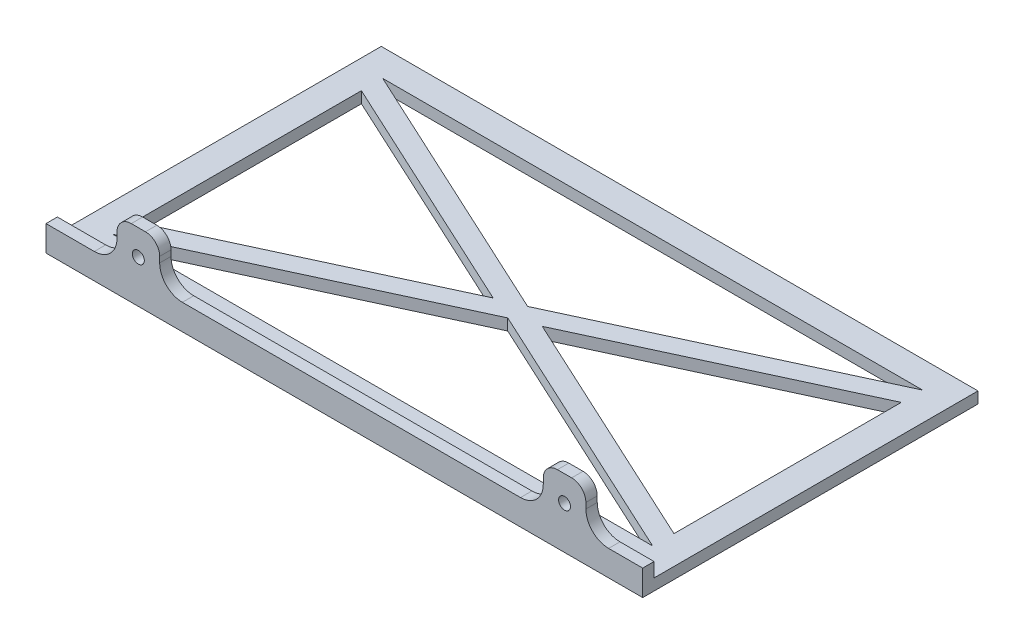
SolidWorks part; units mm, degrees
ref_plane "Спереди" through (0, 0, 0) normal (0, 0, 1) x (1, 0, 0)
ref_plane "Сверху" through (0, 0, 0) normal (0, 1, 0) x (1, 0, 0)
ref_plane "Справа" through (0, 0, 0) normal (1, 0, 0) x (0, 0, -1)
sketch "Эскиз1" plane through (0, 0, 0) normal (0, 1, 0) x (1, 0, 0)
  line L1 (-149.2777, 83.4643) -> (60.7223, 83.4643)
  line L2 (-149.2777, 83.4643) -> (-149.2777, -30.5357)
  line L3 (-149.2777, -30.5357) -> (60.7223, -30.5357)
  line L4 (60.7223, 83.4643) -> (60.7223, -30.5357)
  line L5 (-149.2777, 83.4643) -> (60.7223, -30.5357) construction
  line L6 (-149.2777, -30.5357) -> (60.7223, 83.4643) construction
  point P0 (-44.2777, 26.4643)
  dimension "D1" = 114
  dimension "D2" = 210
extrude "Бобышка-Вытянуть1" add sketch "Эскиз1" along normal blind 4
sketch "Эскиз2" plane through (0, 4, 0) normal (0, 1, 0) x (1, 0, 0)
  line L0 (-139.2777, 73.9643) -> (50.7223, 73.9643)
  line L1 (50.7223, 73.9643) -> (-44.2777, 29.9643)
  line L2 (-44.2777, 29.9643) -> (-139.2777, 73.9643)
  line L3 (-139.2777, -21.0357) -> (50.7223, -21.0357)
  line L4 (50.7223, -21.0357) -> (-44.2777, 22.9643)
  line L5 (-44.2777, 22.9643) -> (-139.2777, -21.0357)
  line L6 (-139.2777, 66.4643) -> (-52.914, 26.4643)
  line L7 (-52.914, 26.4643) -> (-139.2777, -13.5357)
  line L8 (-139.2777, -13.5357) -> (-139.2777, 66.4643)
  line L9 (-35.6413, 26.4643) -> (50.7223, 66.4643)
  line L10 (50.7223, 66.4643) -> (50.7223, -13.5357)
  line L11 (50.7223, -13.5357) -> (-35.6413, 26.4643)
  line L12 (60.7223, 83.4643) -> (-149.2777, 83.4643) construction
  line L13 (-149.2777, -30.5357) -> (60.7223, -30.5357) construction
  line L14 (60.7223, -30.5357) -> (60.7223, 83.4643) construction
  point P11 (-44.2777, 73.9643)
  point P15 (-44.2777, 83.4643)
  point P16 (0, 0)
  point P17 (-44.2777, -21.0357)
  point P20 (-44.2777, -30.5357)
  point P21 (-139.2777, 26.4643)
  point P22 (50.7223, 26.4643)
  point P25 (60.7223, 26.4643)
  point P26 (0, 0)
  dimension "D1" = 190
  dimension "D2" = 80
  dimension "D3" = 44
  dimension "D4" = 44
  dimension "D5" = 7
  dimension "D6" = 9.5
  dimension "D7" = 9.5
extrude "Вырез-Вытянуть1" cut sketch "Эскиз2" against normal through all
sketch "Эскиз5" plane through (0, 0, 30.5357) normal (0, 0, 1) x (1, 0, 0)
  line L0 (-149.2777, 0) -> (60.7223, 0)
  line L1 (60.7223, 0) -> (60.7223, 9)
  line L2 (60.7223, 9) -> (-149.2777, 9)
  line L3 (-149.2777, 9) -> (-149.2777, 0)
  dimension "D1" = 210
  dimension "D2" = 9
extrude "Бобышка-Вытянуть3" add sketch "Эскиз5" along normal blind 4
sketch "Эскиз6" plane through (0, 0, 34.5357) normal (0, 0, 1) x (1, 0, 0)
  line L0 (-124.2777, 9) -> (-124.2777, 24)
  line L1 (60.7223, 9) -> (-149.2777, 9) construction
  line L2 (-124.2777, 24) -> (-109.2777, 24)
  line L3 (-109.2777, 24) -> (-109.2777, 9)
  line L4 (-109.2777, 9) -> (-124.2777, 9)
  line L5 (-149.2777, 9) -> (-149.2777, 0) construction
  line L6 (40.7223, 24) -> (40.7223, 9)
  line L7 (25.7223, 24) -> (40.7223, 24)
  line L8 (25.7223, 9) -> (25.7223, 24)
  line L9 (40.7223, 9) -> (25.7223, 9)
  line L10 (-109.2777, 24) -> (40.7223, 24) construction
  dimension "D1" = 15
  dimension "D2" = 15
  dimension "D3" = 25
  dimension "D5" = 150
  dimension "D4" = 2
extrude "Бобышка-Вытянуть4" add sketch "Эскиз6" against normal blind 4
fillet "Скругление1" radius 8 4 edges at (25.7223, 9, 32.5357) (40.7223, 9, 32.5357) (-109.2777, 9, 32.5357) (-124.2777, 9, 32.5357)
fillet "Скругление2" radius 5 4 edges at (40.7223, 24, 32.5357) (25.7223, 24, 32.5357) (-109.2777, 24, 32.5357) (-124.2777, 24, 32.5357)
sketch "Эскиз7" plane through (0, 0, 34.5357) normal (0, 0, 1) x (1, 0, 0)
  line L0 (-116.7777, 15) -> (33.2223, 15) construction
  line L1 (-149.2777, 0) -> (60.7223, 0) construction
  circle A0 centre (-116.7777, 15) radius 2.1
  circle A1 centre (33.2223, 15) radius 2.1
  dimension "D1" = 4.2
  dimension "D3" = 150
  dimension "D4" = 15
  dimension "D2" = 2
extrude "Вырез-Вытянуть2" cut sketch "Эскиз7" against normal through all
